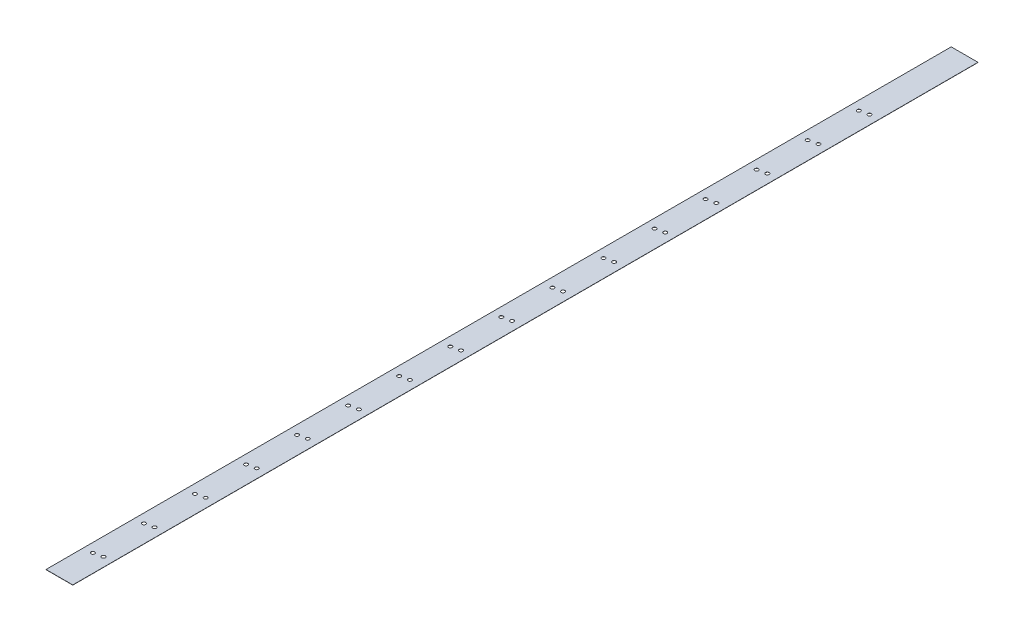
SolidWorks part; units mm, degrees
ref_plane "Front Plane" through (0, 0, 0) normal (0, 0, 1) x (1, 0, 0)
ref_plane "Top Plane" through (0, 0, 0) normal (0, 1, 0) x (1, 0, 0)
ref_plane "Right Plane" through (0, 0, 0) normal (1, 0, 0) x (0, 0, -1)
sketch "Sketch1" plane through (0, 0, 0) normal (0, 1, 0) x (1, 0, 0)
  line L5 (0, 0) -> (15, 0)
  line L6 (0, 0) -> (0, -507)
  line L7 (0, -507) -> (15, -507)
  line L8 (15, 0) -> (15, -507)
  dimension "D1" = 507
  dimension "D2" = 15
extrude "Boss-Extrude1" add sketch "Sketch1" along normal blind 0.1 contours L6 L7 L8 L5
sketch "Sketch2" plane through (0, 0.1, 0) normal (0, 1, 0) x (1, 0, 0)
  line L0 (0, -487) -> (15, -483.537) construction
  line L1 (0, 0) -> (0, -507) construction
  line L2 (15, 0) -> (15, -507) construction
  line L3 (5.0641, -485.8309) -> (5.0641, -457.2309) construction
  circle A0 centre (5.0641, -485.8309) radius 1
  circle A1 centre (9.9359, -484.7061) radius 1
  circle A2 centre (5.0641, -457.2309) radius 1
  circle A3 centre (9.9359, -456.1061) radius 1
  circle A4 centre (5.0641, -428.6309) radius 1
  circle A5 centre (9.9359, -427.5061) radius 1
  circle A6 centre (5.0641, -400.0309) radius 1
  circle A7 centre (9.9359, -398.9061) radius 1
  circle A8 centre (5.0641, -371.4309) radius 1
  circle A9 centre (9.9359, -370.3061) radius 1
  circle A10 centre (5.0641, -342.8309) radius 1
  circle A11 centre (9.9359, -341.7061) radius 1
  circle A12 centre (5.0641, -314.2309) radius 1
  circle A13 centre (9.9359, -313.1061) radius 1
  circle A14 centre (5.0641, -285.6309) radius 1
  circle A15 centre (9.9359, -284.5061) radius 1
  circle A16 centre (5.0641, -257.0309) radius 1
  circle A17 centre (9.9359, -255.9061) radius 1
  circle A18 centre (5.0641, -228.4309) radius 1
  circle A19 centre (9.9359, -227.3061) radius 1
  circle A20 centre (5.0641, -199.8309) radius 1
  circle A21 centre (9.9359, -198.7061) radius 1
  circle A22 centre (5.0641, -171.2309) radius 1
  circle A23 centre (9.9359, -170.1061) radius 1
  circle A24 centre (5.0641, -142.6309) radius 1
  circle A25 centre (9.9359, -141.5061) radius 1
  circle A26 centre (5.0641, -114.0309) radius 1
  circle A27 centre (9.9359, -112.9061) radius 1
  circle A28 centre (5.0641, -85.4309) radius 1
  circle A29 centre (9.9359, -84.3061) radius 1
  circle A30 centre (5.0641, -56.8309) radius 1
  circle A31 centre (9.9359, -55.7061) radius 1
  point P13 (7.5, -485.2685)
  dimension "D3" = 2
  dimension "D4" = 5
  dimension "D1" = 20
  dimension "D2" = 77
  dimension "D5" = 2.5
  dimension "D7" = 28.6
  dimension "D6" = 16
extrude "Cut-Extrude1" cut sketch "Sketch2" against normal through all
